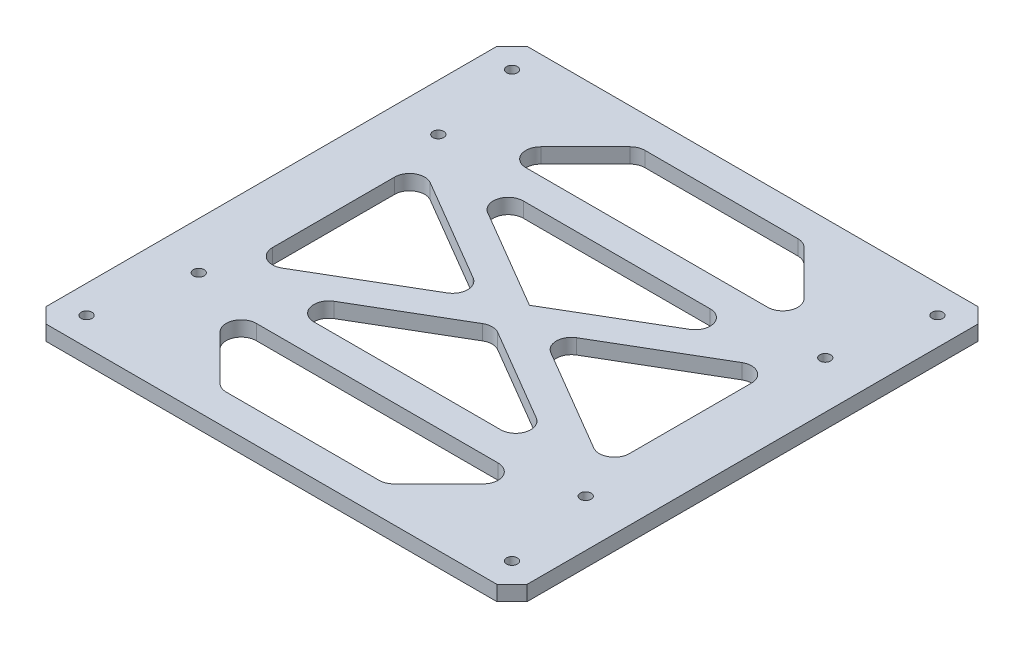
SolidWorks part; units mm, degrees
ref_plane "Front Plane" through (0, 0, 0) normal (0, 0, 1) x (1, 0, 0)
ref_plane "Top Plane" through (0, 0, 0) normal (0, 1, 0) x (1, 0, 0)
ref_plane "Right Plane" through (0, 0, 0) normal (1, 0, 0) x (0, 0, -1)
sketch "Sketch1" plane through (0, 0, 0) normal (0, 1, 0) x (1, 0, 0)
  line L0 (0, 196.85) -> (6.35, 203.2)
  line L1 (6.35, 0) -> (196.85, 0)
  line L2 (0, 6.35) -> (0, 196.85)
  line L3 (6.35, 203.2) -> (196.85, 203.2)
  line L4 (203.2, 6.35) -> (203.2, 196.85)
  line L5 (196.85, 203.2) -> (203.2, 196.85)
  line L6 (196.85, 0) -> (203.2, 6.35)
  line L7 (0, 6.35) -> (6.35, 0)
  point P0 (0, 0)
  point P1 (203.2, 203.2)
  point P2 (0, 203.2)
  point P3 (203.2, 0)
  dimension "D1" = 203.2
  dimension "D2" = 203.2
extrude "Boss-Extrude1" add sketch "Sketch1" along normal blind 6.35
sketch "Sketch3" plane through (0, 6.35, 0) normal (0, 1, 0) x (1, 0, 0)
  line L0 (6.35, 0) -> (196.85, 0) construction
  line L1 (0, 196.85) -> (0, 6.35) construction
  line L2 (203.2, 6.35) -> (203.2, 196.85) construction
  line L3 (196.85, 203.2) -> (6.35, 203.2) construction
  circle A0 centre (11.7373, 11.7373) radius 2.286
  circle A1 centre (191.4627, 11.7373) radius 2.286
  circle A2 centre (191.4627, 191.4627) radius 2.286
  circle A3 centre (11.7373, 191.4627) radius 2.286
  dimension "D1" = 2
  dimension "D3" = 4.572
  dimension "D4" = 11.7373
  dimension "D5" = 11.7373
  dimension "D6" = 11.7373
  dimension "D7" = 11.7373
  dimension "D8" = 11.7373
  dimension "D2" = 2
extrude "Cut-Extrude2" cut sketch "Sketch3" against normal through all
sketch "Sketch4" plane through (0, 6.35, 0) normal (0, 1, 0) x (1, 0, 0)
  line L0 (0, 196.85) -> (0, 6.35) construction
  line L1 (19.8692, 152.1955) -> (183.3308, 152.1955) construction
  line L2 (19.8692, 152.1955) -> (19.8692, 51.0045) construction
  line L3 (19.8692, 51.0045) -> (183.3308, 51.0045) construction
  line L4 (183.3308, 152.1955) -> (183.3308, 51.0045) construction
  line L5 (196.85, 203.2) -> (6.35, 203.2) construction
  line L6 (16.6942, 140.0403) -> (66.6884, 190.0345)
  line L7 (136.5116, 190.0345) -> (66.6884, 190.0345)
  line L8 (136.5116, 190.0345) -> (186.5058, 140.0403)
  line L9 (186.5058, 63.1597) -> (136.5116, 13.1655)
  line L10 (186.5058, 140.0403) -> (186.5058, 63.1597)
  line L11 (136.5116, 13.1655) -> (66.6884, 13.1655)
  line L12 (66.6884, 13.1655) -> (16.6942, 63.1597)
  line L13 (16.6942, 63.1597) -> (16.6942, 140.0403)
  circle A0 centre (19.8692, 152.1955) radius 2.286
  circle A1 centre (183.3308, 152.1955) radius 2.286
  circle A2 centre (183.3308, 51.0045) radius 2.286
  circle A3 centre (19.8692, 51.0045) radius 2.286
  point P6 (0, 101.6)
  point P7 (19.8692, 101.6)
  point P10 (101.6, 203.2)
  point P11 (101.6, 152.1955)
  dimension "D3" = 4.572
  dimension "D5" = 6.35
  dimension "D7" = 6.35
  dimension "D1" = 163.4617
  dimension "D2" = 101.1911
  dimension "D4" = 6.35
  dimension "D6" = 6.35
  dimension "D8" = 6.35
extrude "Cut-Extrude3" cut sketch "Sketch4" against normal through all
sketch "Sketch5" plane through (0, 6.35, 0) normal (0, 1, 0) x (1, 0, 0)
  line L0 (19.8692, 51.0045) -> (183.3308, 51.0045) construction
  line L1 (183.3308, 51.0045) -> (183.3308, 152.1955) construction
  line L2 (183.3308, 152.1955) -> (19.8692, 152.1955) construction
  line L3 (19.8692, 152.1955) -> (19.8692, 51.0045) construction
  line L4 (189.6808, 158.5455) -> (13.5192, 158.5455)
  line L5 (13.5192, 158.5455) -> (13.5192, 44.6545)
  line L6 (13.5192, 44.6545) -> (189.6808, 44.6545)
  line L7 (189.6808, 44.6545) -> (189.6808, 158.5455)
  line L8 (141.0736, 145.8455) -> (62.1264, 145.8455)
  line L9 (26.2192, 127.3922) -> (26.2192, 75.8078)
  line L10 (62.1264, 57.3545) -> (141.0736, 57.3545)
  line L11 (176.9808, 75.8078) -> (176.9808, 127.3922)
  line L12 (26.2192, 57.3545) -> (176.9808, 145.8455) construction
  line L13 (176.9808, 57.3545) -> (26.2192, 145.8455) construction
  line L14 (58.912, 69.1808) -> (98.3856, 92.3502)
  line L15 (167.4165, 70.3314) -> (123.4744, 96.1237)
  line L16 (35.7835, 70.3314) -> (79.7256, 96.1237)
  line L17 (144.288, 69.1808) -> (104.8144, 92.3502)
  line L18 (180.1952, 62.8308) -> (29.4335, 151.3219) construction
  line L19 (173.7665, 51.8781) -> (23.0048, 140.3692) construction
  line L20 (23.0048, 62.8308) -> (173.7665, 151.3219) construction
  line L21 (29.4335, 51.8781) -> (180.1952, 140.3692) construction
  line L22 (26.2192, 57.3545) -> (176.9808, 57.3545) construction
  line L23 (176.9808, 57.3545) -> (176.9808, 145.8455) construction
  line L24 (176.9808, 145.8455) -> (26.2192, 145.8455) construction
  line L25 (26.2192, 145.8455) -> (26.2192, 57.3545) construction
  line L26 (79.7256, 107.0763) -> (35.7835, 132.8686)
  line L27 (101.6, 108.963) -> (144.288, 134.0192)
  line L28 (123.4744, 107.0763) -> (167.4165, 132.8686)
  line L29 (101.6, 108.963) -> (58.912, 134.0192)
  circle A0 centre (183.3308, 51.0045) radius 2.286 construction
  circle A1 centre (183.3308, 152.1955) radius 2.286 construction
  circle A2 centre (19.8692, 152.1955) radius 2.286 construction
  circle A3 centre (19.8692, 51.0045) radius 2.286 construction
  circle A4 centre (183.3308, 51.0045) radius 2.286
  circle A5 centre (183.3308, 152.1955) radius 2.286
  circle A6 centre (19.8692, 152.1955) radius 2.286
  circle A7 centre (19.8692, 51.0045) radius 2.286
  arc A8 (58.912, 134.0192) -> (62.1264, 145.8455) centre (62.1264, 139.4955) cw
  arc A9 (144.288, 134.0192) -> (141.0736, 145.8455) centre (141.0736, 139.4955) ccw
  arc A10 (167.4165, 132.8686) -> (176.9808, 127.3922) centre (170.6308, 127.3922) cw
  arc A11 (123.4744, 107.0763) -> (123.4744, 96.1237) centre (126.6888, 101.6) ccw
  arc A12 (167.4165, 70.3314) -> (176.9808, 75.8078) centre (170.6308, 75.8078) ccw
  arc A13 (144.288, 69.1808) -> (141.0736, 57.3545) centre (141.0736, 63.7045) cw
  arc A14 (104.8144, 92.3502) -> (98.3856, 92.3502) centre (101.6, 86.8739) ccw
  arc A15 (79.7256, 107.0763) -> (79.7256, 96.1237) centre (76.5112, 101.6) cw
  arc A16 (35.7835, 132.8686) -> (26.2192, 127.3922) centre (32.5692, 127.3922) ccw
  arc A17 (35.7835, 70.3314) -> (26.2192, 75.8078) centre (32.5692, 75.8078) cw
  arc A18 (58.912, 69.1808) -> (62.1264, 57.3545) centre (62.1264, 63.7045) ccw
  dimension "D5" = 6.35
  dimension "D1" = 6.35
  dimension "D3" = 6.35
  dimension "D2" = 6.35
  dimension "D4" = 6.35
extrude "Boss-Extrude2" add sketch "Sketch5" against normal up to surface (6.35 mm away) up to face at (183.3308, 0, -149.9095)
fillet "Fillet1" radius 6.35 8 edges at (136.5116, 3.175, -190.0345) (66.6884, 3.175, -190.0345) (35.1994, 3.175, -158.5455) (168.0006, 3.175, -158.5455) (66.6884, 3.175, -13.1655) (35.1994, 3.175, -44.6545) (136.5116, 3.175, -13.1655) (168.0006, 3.175, -44.6545)
